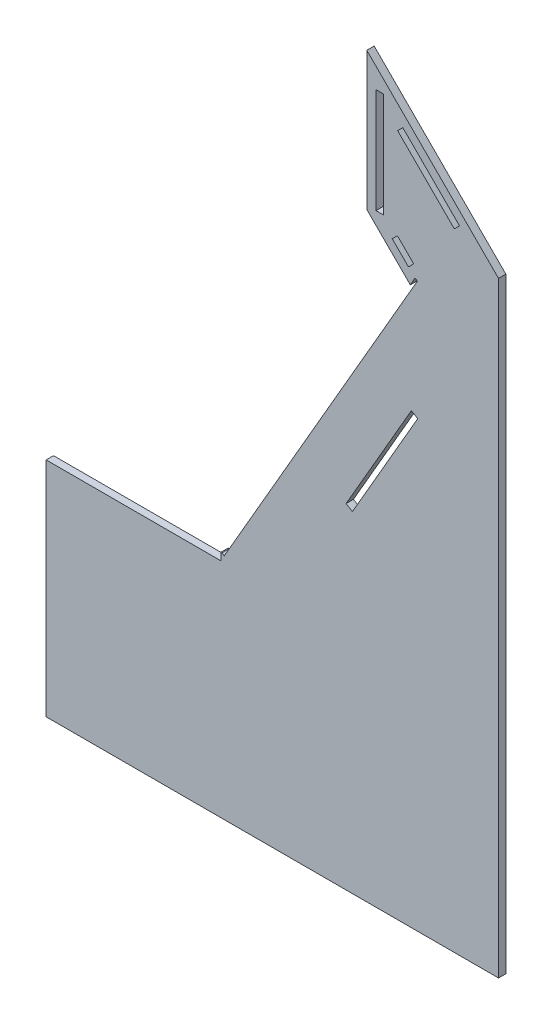
SolidWorks part; units mm, degrees
ref_plane "Front Plane" through (0, 0, 0) normal (0, 0, 1) x (1, 0, 0)
ref_plane "Top Plane" through (0, 0, 0) normal (0, 1, 0) x (1, 0, 0)
ref_plane "Right Plane" through (0, 0, 0) normal (1, 0, 0) x (0, 0, -1)
sketch "Sketch1" plane through (0, 0, 0) normal (0, 0, 1) x (1, 0, 0)
  line L0 (0, 242) -> (190, 242) construction
  line L1 (0, 0) -> (492, 0)
  line L2 (0, 0) -> (0, 242)
  line L3 (0, 242) -> (190, 242)
  line L5 (190, 242) -> (398.25, 602.6996)
  line L6 (398.25, 602.6996) -> (348.7525, 652.1971)
  line L7 (348.7525, 652.1971) -> (348.7525, 802.1971)
  line L8 (348.7525, 802.1971) -> (492, 658.9496)
  line L9 (492, 658.9496) -> (492, 0)
  line L10 (190, 242) -> (190, 250)
  line L11 (190, 250) -> (191.15, 250)
  line L12 (191.15, 250) -> (193.7516, 248.498)
  line L13 (398.25, 602.6996) -> (403.7516, 612.2286)
  line L14 (403.7516, 612.2286) -> (401.1535, 613.7286)
  line L15 (401.1535, 613.7286) -> (396.0538, 604.8957)
  line L16 (191.1535, 249.998) -> (401.1535, 613.7286) construction
  line L17 (376.4048, 638.4774) -> (394.0825, 620.7997) construction
  line L18 (394.0825, 620.7997) -> (399.7393, 626.4566) construction
  line L19 (399.7393, 626.4566) -> (382.0616, 644.1342) construction
  line L20 (382.0616, 644.1342) -> (376.4048, 638.4774) construction
  line L21 (333.1433, 359.9314) -> (404.1433, 482.907)
  line L22 (404.1433, 482.907) -> (397.215, 486.907)
  line L23 (397.215, 486.907) -> (326.215, 363.9314)
  line L24 (326.215, 363.9314) -> (333.1433, 359.9314)
  line L25 (333.1433, 359.9314) -> (404.1433, 482.907)
  line L26 (404.1433, 482.907) -> (397.215, 486.907)
  line L27 (397.215, 486.907) -> (326.215, 363.9314)
  line L28 (326.215, 363.9314) -> (333.1433, 359.9314)
  line L29 (366.7271, 656.155) -> (366.7271, 770.085) construction
  line L30 (366.7271, 770.085) -> (358.7271, 770.085) construction
  line L31 (358.7271, 770.085) -> (358.7271, 656.155) construction
  line L32 (358.7271, 656.155) -> (366.7271, 656.155) construction
  line L33 (382.2835, 743.215) -> (443.9149, 681.5836) construction
  line L34 (443.9149, 681.5836) -> (449.5717, 687.2404) construction
  line L35 (449.5717, 687.2404) -> (387.9403, 748.8718) construction
  line L36 (387.9403, 748.8718) -> (382.2835, 743.215) construction
  line L37 (376.4048, 638.4774) -> (394.0825, 620.7997)
  line L38 (394.0825, 620.7997) -> (399.7393, 626.4566)
  line L39 (399.7393, 626.4566) -> (382.0616, 644.1342)
  line L40 (382.0616, 644.1342) -> (376.4048, 638.4774)
  line L41 (366.7271, 656.155) -> (366.7271, 770.085)
  line L42 (366.7271, 770.085) -> (358.7271, 770.085)
  line L43 (358.7271, 770.085) -> (358.7271, 656.155)
  line L44 (358.7271, 656.155) -> (366.7271, 656.155)
  line L45 (382.2835, 743.215) -> (443.9149, 681.5836)
  line L46 (443.9149, 681.5836) -> (449.5717, 687.2404)
  line L47 (449.5717, 687.2404) -> (387.9403, 748.8718)
  line L48 (387.9403, 748.8718) -> (382.2835, 743.215)
  dimension "D3" = 60
  dimension "D1" = 492
  dimension "D2" = 242
  dimension "D4" = 416.5
  dimension "D5" = 190
  dimension "D6" = 150
  dimension "D7" = 70
  dimension "D8" = 105
  dimension "D9" = 8
  dimension "D10" = 1.15
  dimension "D11" = 0
extrude "Boss-Extrude1" add sketch "Sketch1" along normal blind 8 contours L12 L11 L10 L5 | L15 L14 L13 L5 L3 L2 L1 L9 L8 L7 L6 region at (305.9067, 254.6671, 0) region at (191.2714, 246.9778, 0)
